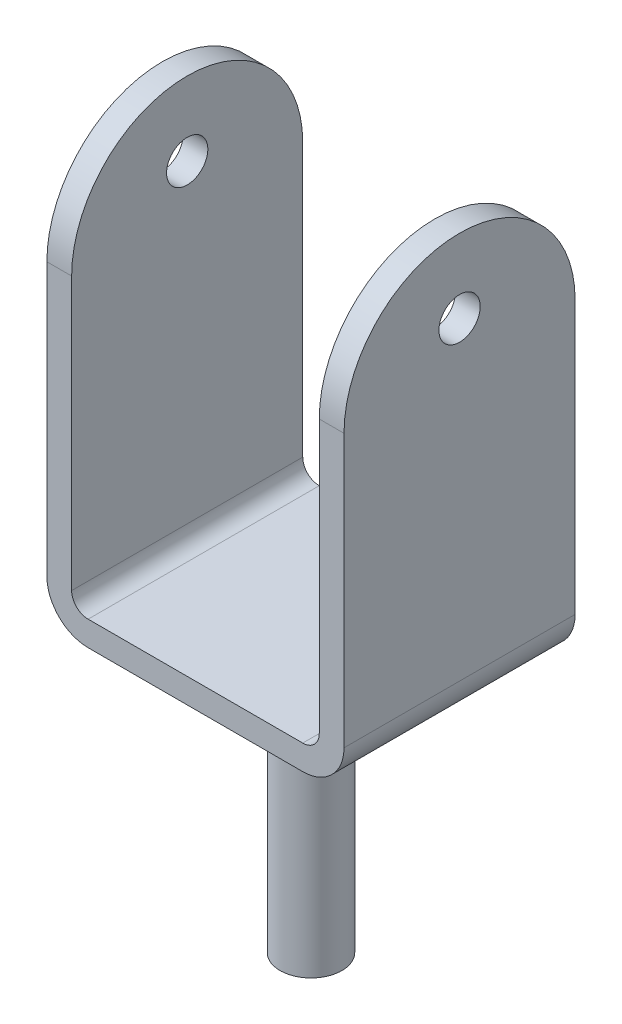
SolidWorks part; units mm, degrees
ref_plane "Front Plane" through (0, 0, 0) normal (0, 0, 1) x (1, 0, 0)
ref_plane "Top Plane" through (0, 0, 0) normal (0, 1, 0) x (1, 0, 0)
ref_plane "Right Plane" through (0, 0, 0) normal (1, 0, 0) x (0, 0, -1)
sketch "Sketch1" plane through (0, 0, 0) normal (0, 0, 1) x (1, 0, 0)
  line L0 (-167.5, 325) -> (92.5, 325)
  line L1 (0, 0) -> (-75, 0)
  line L2 (0, 0) -> (0, 325)
  line L3 (0, 325) -> (-75, 325)
  line L4 (-75, 0) -> (-75, 325)
  line L5 (142.5, 375) -> (142.5, 845)
  line L6 (-217.5, 375) -> (-217.5, 845)
  line L7 (112.5, 375) -> (112.5, 845)
  line L8 (-167.5, 355) -> (92.5, 355)
  line L9 (-187.5, 375) -> (-187.5, 845)
  line L10 (142.5, 845) -> (112.5, 845)
  line L11 (-217.5, 845) -> (-187.5, 845)
  line L12 (-217.5, 325) -> (142.5, 325) construction
  line L13 (-217.5, 325) -> (-217.5, 845) construction
  line L14 (142.5, 325) -> (142.5, 845) construction
  line L15 (-187.5, 355) -> (112.5, 355) construction
  line L16 (-187.5, 355) -> (-187.5, 845) construction
  line L17 (112.5, 355) -> (112.5, 845) construction
  line L18 (-37.5, 325) -> (-37.5, 0)
  arc A0 (-167.5, 325) -> (-217.5, 375) centre (-167.5, 375) cw
  arc A1 (92.5, 325) -> (142.5, 375) centre (92.5, 375) ccw
  arc A2 (-167.5, 355) -> (-187.5, 375) centre (-167.5, 375) cw
  arc A3 (112.5, 375) -> (92.5, 355) centre (92.5, 375) cw
  point P8 (-37.5, 325)
  point P17 (-217.5, 325)
  dimension "D7" = 50
  dimension "D2" = 20
  dimension "D1" = 325
  dimension "D3" = 520
  dimension "D4" = 360
  dimension "D5" = 75
  dimension "D6" = 30
extrude "Boss-Extrude1" add sketch "Sketch1" along normal mid plane 280 contours L7 A3 L8 A2 L9 L11 L6 A0 L0 A1 L5 L10 region at (-198.3832, 344.1168, 0)
revolve "Revolve1" add sketch "Sketch1<4>" angle 360 about L18 region at (-18.75, 162.5, 0)
sketch "Sketch1<4>" plane through (0, 0, 0) normal (0, 0, 1) x (1, 0, 0) same geometry as "Sketch1"
sketch "Sketch2" plane through (142.5, 0, 0) normal (1, 0, 0) x (0, 0, -1)
  line L0 (140, 375) -> (140, 845) construction
  circle A0 centre (0, 755.5721) radius 25
  dimension "D1" = 50
  dimension "D2" = 140
extrude "Cut-Extrude1" cut sketch "Sketch2" against normal through all
fillet "Fillet3" 2 edges at (127.5, 845, 140) (127.5, 845, -140) type full round first side face at (-37.5, 517.5838, 140) second side face at (-37.5, 517.5838, -140) middle face at (127.5, 845, 0)
fillet "Fillet4" 2 edges at (-202.5, 845, 140) (-202.5, 845, -140) type full round first side face at (-37.5, 494.2504, 140) second side face at (-37.5, 494.2504, -140) middle face at (-202.5, 845, 0)
